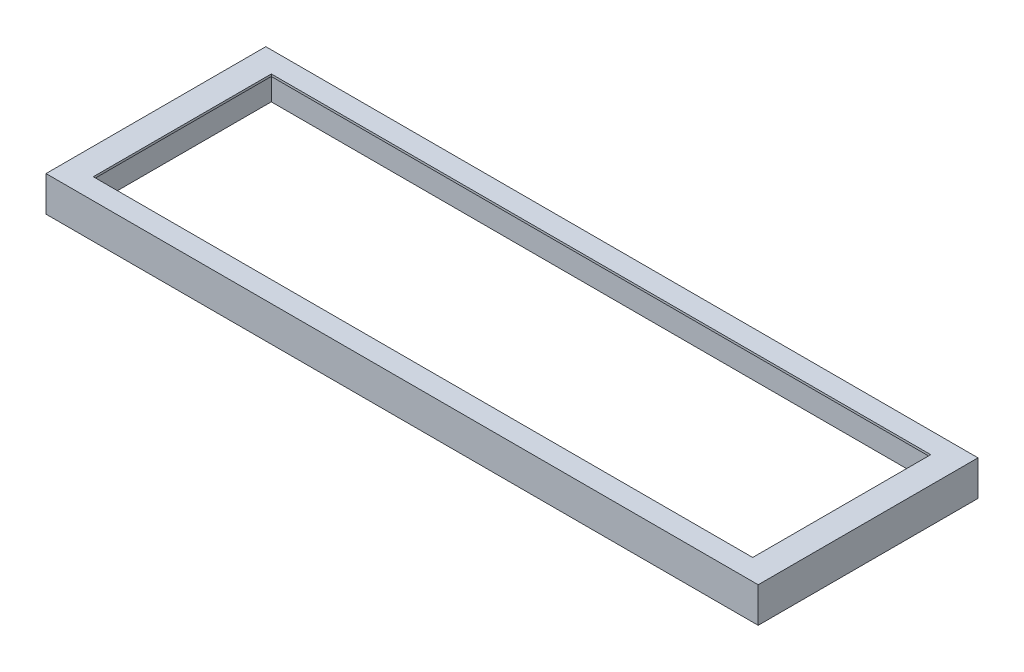
SolidWorks part; units mm, degrees
ref_plane "Alzado" through (0, 0, 0) normal (0, 0, 1) x (1, 0, 0)
ref_plane "Planta" through (0, 0, 0) normal (0, 1, 0) x (1, 0, 0)
ref_plane "Vista lateral" through (0, 0, 0) normal (1, 0, 0) x (0, 0, -1)
sketch "Croquis1" plane through (0, 0, 0) normal (0, 1, 0) x (1, 0, 0)
  line L1 (-514.35, -158.75) -> (514.35, -158.75)
  line L2 (-514.35, -158.75) -> (-514.35, 158.75)
  line L3 (-514.35, 158.75) -> (514.35, 158.75)
  line L4 (514.35, -158.75) -> (514.35, 158.75)
  line L5 (-514.35, -158.75) -> (514.35, 158.75) construction
  line L6 (-514.35, 158.75) -> (514.35, -158.75) construction
  line L7 (-447.675, -100.0125) -> (447.675, -100.0125)
  line L8 (-447.675, -100.0125) -> (-447.675, 100.0125)
  line L9 (-447.675, 100.0125) -> (447.675, 100.0125)
  line L10 (447.675, -100.0125) -> (447.675, 100.0125)
  line L11 (-447.675, -100.0125) -> (447.675, 100.0125) construction
  line L12 (-447.675, 100.0125) -> (447.675, -100.0125) construction
  line L13 (-476.25, -128.5875) -> (476.25, -128.5875)
  line L14 (-476.25, -128.5875) -> (-476.25, 128.5875)
  line L15 (-476.25, 128.5875) -> (476.25, 128.5875)
  line L16 (476.25, -128.5875) -> (476.25, 128.5875)
  line L17 (-476.25, -128.5875) -> (476.25, 128.5875) construction
  line L18 (-476.25, 128.5875) -> (476.25, -128.5875) construction
  point P0 (0, 0)
  point P6 (0, 0)
  point P11 (0, 0)
  dimension "D1" = 1028.7
  dimension "D2" = 317.5
  dimension "D3" = 200.025
  dimension "D4" = 895.35
  dimension "D5" = 28.575
  dimension "D6" = 28.575
extrude "Saliente-Extruir1" add sketch "Croquis1" along normal blind 50.8 contours L13 L16 L15 L14 L10 L7 L8 L9 | L1 L4 L3 L2 L16 L13 L14 L15 | L7 L10 L9 L8 region at (-503.5842, 0, 0) region at (0, 0, 0) region at (-466.3839, 0, 0)
sketch "Croquis6" plane through (0, 0, 0) normal (0, -1, 0) x (-1, 0, 0)
  line L1 (447.675, 100.0125) -> (-447.675, 100.0125)
  line L2 (447.675, 100.0125) -> (447.675, -100.0125)
  line L3 (447.675, -100.0125) -> (-447.675, -100.0125)
  line L4 (-447.675, 100.0125) -> (-447.675, -100.0125)
  line L5 (447.675, 100.0125) -> (-447.675, -100.0125) construction
  line L6 (447.675, -100.0125) -> (-447.675, 100.0125) construction
  line L7 (492.125, 144.4625) -> (-492.125, 144.4625)
  line L8 (492.125, 144.4625) -> (492.125, -144.4625)
  line L9 (492.125, -144.4625) -> (-492.125, -144.4625)
  line L10 (-492.125, 144.4625) -> (-492.125, -144.4625)
  line L11 (492.125, 144.4625) -> (-492.125, -144.4625) construction
  line L12 (492.125, -144.4625) -> (-492.125, 144.4625) construction
  point P0 (0, 0)
  point P6 (0, 0)
  dimension "D1" = 895.35
  dimension "D2" = 200.025
  dimension "D3" = 44.45
  dimension "D4" = 44.45
extrude "Cortar-Extruir6" cut sketch "Croquis6" against normal blind 47.625 contours L1 L4 L3 L2 | L7 L10 L9 L8 L4 L1 L2 L3 region at (0, 0, 0) region at (-481.8672, 0, 0)
extrude "Cortar-Extruir1" cut sketch "Croquis1<4>" along normal through all contours L7 L10 L9 L8 region at (0, 0, 0)
sketch "Croquis1<4>" plane through (0, 0, 0) normal (0, 1, 0) x (1, 0, 0) same geometry as "Croquis1"
sketch "Croquis7" plane through (0, 50.8, 0) normal (0, 1, 0) x (1, 0, 0)
  line L0 (447.675, -100.0125) -> (447.675, 100.0125) construction
  line L1 (476.25, 128.5875) -> (-476.25, 128.5875)
  line L2 (476.25, 128.5875) -> (476.25, -128.5875)
  line L3 (476.25, -128.5875) -> (-476.25, -128.5875)
  line L4 (-476.25, 128.5875) -> (-476.25, -128.5875)
  line L5 (476.25, 128.5875) -> (-476.25, -128.5875) construction
  line L6 (476.25, -128.5875) -> (-476.25, 128.5875) construction
  line L7 (-447.675, -100.0125) -> (447.675, -100.0125) construction
  point P0 (0, 0)
  dimension "D1" = 28.575
  dimension "D2" = 28.575
extrude "Cortar-Extruir7" cut sketch "Croquis7" against normal through all
